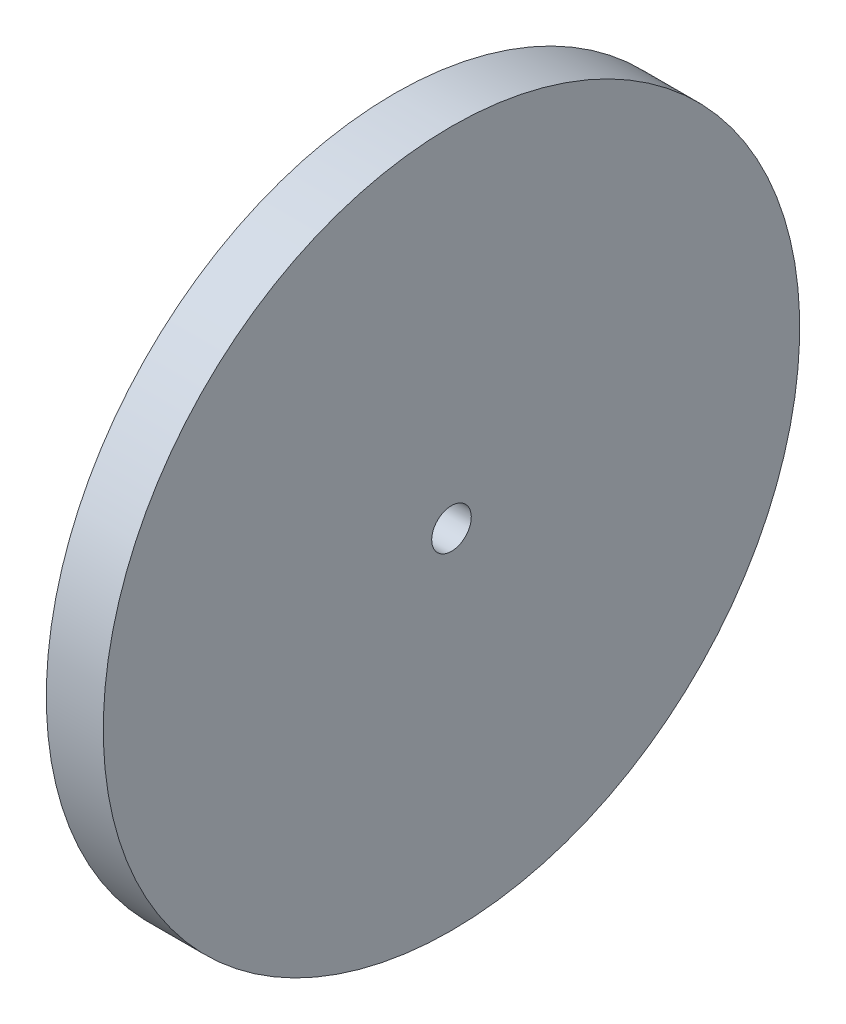
SolidWorks part; units mm, degrees
ref_plane "Front Plane" through (0, 0, 0) normal (0, 0, 1) x (1, 0, 0)
ref_plane "Top Plane" through (0, 0, 0) normal (0, 1, 0) x (1, 0, 0)
ref_plane "Right Plane" through (0, 0, 0) normal (1, 0, 0) x (0, 0, -1)
sketch "Sketch1" plane through (0, 0, 0) normal (0, 0, 1) x (1, 0, 0)
  line L0 (0, 15) -> (-58, 15)
  line L1 (0, 0) -> (-58, 0)
  line L2 (0, 0) -> (0, 15)
  line L4 (-58, 0) -> (-58, 15)
  line L6 (-58, 15) -> (0, 15)
  line L7 (-58, 15) -> (-58, 22)
  line L8 (-58, 22) -> (0, 22)
  line L9 (0, 15) -> (0, 22)
  line L10 (-54.4, 22) -> (-54.4, 15)
  line L11 (-29, 22) -> (-29, 15) construction
  line L12 (-3.6, 22) -> (-3.6, 15)
  dimension "D1" = 15
  dimension "D2" = 50.8
  dimension "D3" = 7
  dimension "D4" = 3.6
revolve "Revolve1" add sketch "Sketch1" angle 360 about L1 region at (-29, 7.5, 0) region at (-1.8, 18.5, 0) region at (-56.2, 18.5, 0)
sketch "Sketch2" plane through (-58, 0, 0) normal (-1, 0, 0) x (0, 0, 1)
  circle A0 centre (0, 0) radius 1.25
  dimension "D1" = 2.5
extrude "Cut-Extrude1" cut sketch "Sketch2" against normal through all
sketch "Sketch3" plane through (0, 0, 0) normal (1, 0, 0) x (0, 0, -1)
  circle A0 centre (0, 0) radius 22
  circle A1 centre (0, 0) radius 22 construction
extrude "Cut-Extrude2" cut sketch "Sketch3" against normal up to surface (54.4 mm away) up to face at (-54.4, 15, 0)
